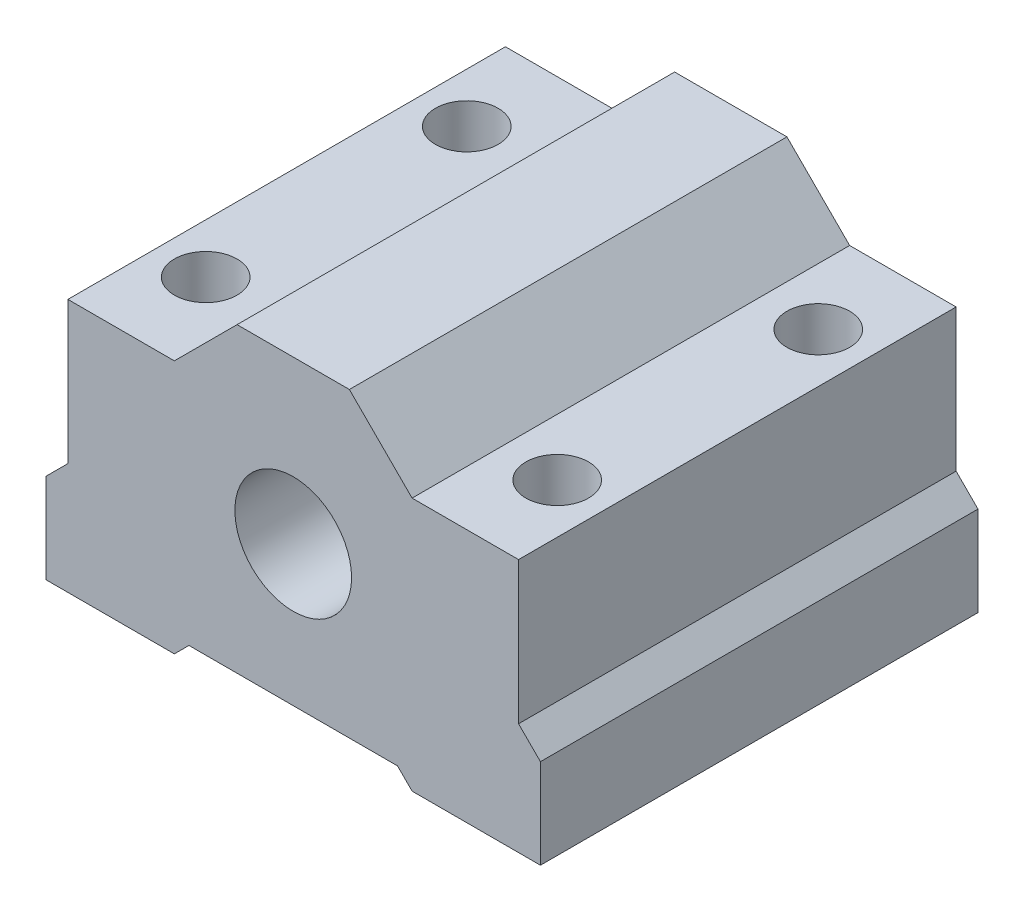
SolidWorks part; units mm, degrees
ref_plane "Front Plane" through (0, 0, 0) normal (0, 0, 1) x (1, 0, 0)
ref_plane "Top Plane" through (0, 0, 0) normal (0, 1, 0) x (1, 0, 0)
ref_plane "Right Plane" through (0, 0, 0) normal (1, 0, 0) x (0, 0, -1)
sketch "Sketch1" plane through (0, 0, 0) normal (0, 0, 1) x (1, 0, 0)
  line L0 (0, 0) -> (0, 6.15)
  line L1 (0, 6.15) -> (1.5, 7.65)
  line L2 (1.5, 7.65) -> (1.5, 17.4)
  line L3 (1.5, 17.4) -> (8.8, 17.4)
  line L4 (8.8, 17.4) -> (13.1, 21.7)
  line L5 (13.1, 21.7) -> (20.8, 21.7)
  line L6 (20.8, 21.7) -> (25.1, 17.4)
  line L7 (25.1, 17.4) -> (32.4, 17.4)
  line L8 (32.4, 17.4) -> (32.4, 7.65)
  line L9 (32.4, 7.65) -> (33.9, 6.15)
  line L10 (33.9, 6.15) -> (33.9, 0)
  line L12 (0, 0) -> (8.8, 0)
  line L13 (8.8, 0) -> (9.8, 1)
  line L14 (9.8, 1) -> (24.1, 1)
  line L15 (24.1, 1) -> (25.1, 0)
  line L16 (25.1, 0) -> (33.9, 0)
  circle A0 centre (16.95, 10.6) radius 4
  point P19 (16.95, 6.6)
  point P21 (16.95, 21.7)
  point P22 (16.95, 1)
  dimension "D9" = 8
  dimension "D1" = 33.9
  dimension "D2" = 17.4
  dimension "D3" = 45
  dimension "D4" = 7.3
  dimension "D5" = 20.7
  dimension "D6" = 4.3
  dimension "D7" = 30.9
  dimension "D8" = 7.65
  dimension "D10" = 5.6
extrude "Boss-Extrude1" add sketch "Sketch1" along normal blind 30
hole_wizard "CSK for M4 Hex Socket Countersunk Cap Screw1" positions "Sketch2" profile "Sketch4" countersink size "M4" standard "ISO" end condition through all
sketch "Sketch2" plane through (0, 0, 0) normal (0, -1, 0) x (-1, 0, 0)
  line L0 (-4.9, -6.05) -> (-4.9, -23.95) construction
  line L2 (-4.9, -6.05) -> (-29, -6.05) construction
  line L4 (-9.8, 0) -> (-24.1, 0) construction
  line L5 (0, -30) -> (0, 0) construction
  point P0 (-4.9, -6.05)
  point P2 (-4.9, -23.95)
  point P4 (-29, -6.05)
  point P6 (-29, -23.95)
  point P32 (-16.95, 0)
  point P33 (-16.95, -6.05)
  point P36 (0, -15)
  point P37 (-4.9, -15)
  dimension "D1" = 17.9
  dimension "D2" = 24.1
sketch "Sketch4" plane through (4.9, 0, 6.05) normal (1, 0, 0) x (0, 0, -1)
  line L0 (0, 0) -> (0, 21.7)
  line L1 (0, 21.7) -> (2.15, 21.7)
  line L2 (2.15, 21.7) -> (2.15, 0.83)
  line L3 (2.15, 0.83) -> (2.98, 0)
  line L5 (2.98, 0) -> (0, 0)
  line L6 (-2.15, 0.83) -> (-2.98, 0) construction
  line L11 (0, -6.35) -> (0, 107.95) construction
  dimension "Thru Hole Dia." = 4.3
  dimension "Thru Hole Depth" = 21.7
  dimension "Near C'Sink Dia." = 5.96
  dimension "Near C'Sink Angle" = 90
ref_axis "Axis1" through (29, 17.4, 6.05) along (0, -1, 0)
ref_axis "Axis2" through (4.9, 17.4, 6.05) along (0, -1, 0)
ref_plane "Plane1" through (0, 0, 6.05) normal (0, 0, 1) x (1, 0, 0)
